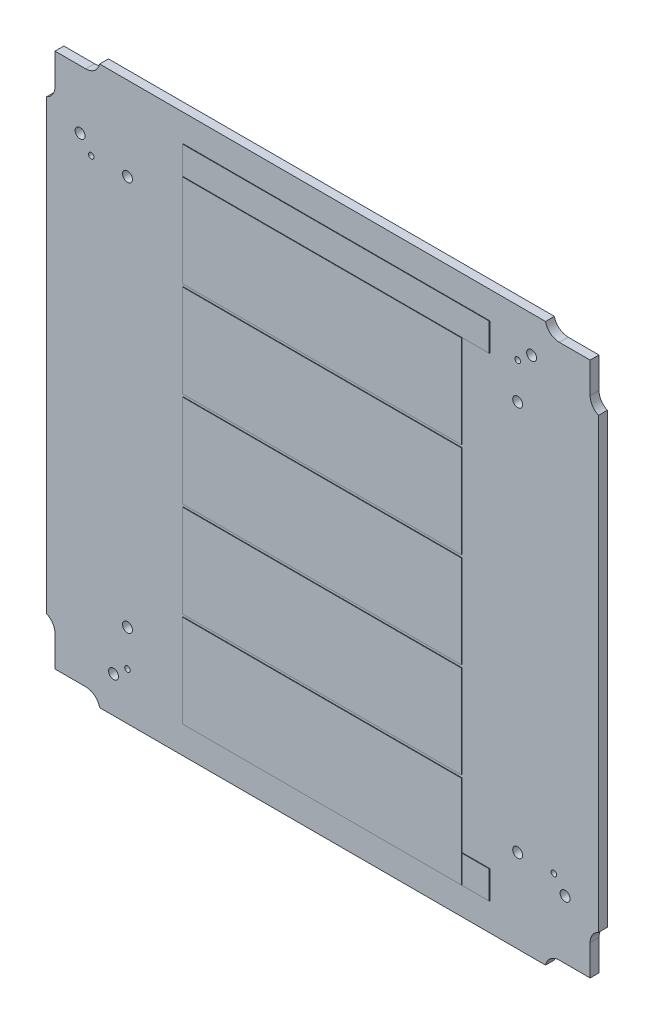
SolidWorks part; units mm, degrees
ref_plane "Front Plane" through (0, 0, 0) normal (0, 0, 1) x (1, 0, 0)
ref_plane "Top Plane" through (0, 0, 0) normal (0, 1, 0) x (1, 0, 0)
ref_plane "Right Plane" through (0, 0, 0) normal (1, 0, 0) x (0, 0, -1)
sketch "Sketch1" plane through (0, 0, 0) normal (0, 0, 1) x (1, 0, 0)
  line L0 (-40, 50) -> (-40, 48)
  line L1 (-50, -50) -> (50, -50)
  line L2 (-50, -50) -> (-50, 50)
  line L3 (-50, 50) -> (50, 50)
  line L4 (50, -50) -> (50, 50)
  line L5 (-50, -50) -> (50, 50) construction
  line L6 (-50, 50) -> (50, -50) construction
  line L7 (-50, 50) -> (-40, 50)
  line L8 (-50, 50) -> (-50, 40)
  line L9 (-40, 48) -> (-48, 48)
  line L10 (-48, 48) -> (-48, 40)
  line L11 (50, 50) -> (40, 50)
  line L12 (50, 50) -> (50, 40)
  line L13 (-48, 40) -> (-50, 40)
  line L14 (50, 40) -> (48, 40)
  line L15 (-50, -50) -> (-37.8649, -50)
  line L16 (-50, -50) -> (-50, -37.8649)
  line L17 (50, 50) -> (50, 40)
  line L18 (50, 50) -> (40, 50)
  line L19 (50, -50) -> (41.5, -50)
  line L20 (50, -50) -> (50, -41.5)
  line L21 (48, 40) -> (48, 48)
  line L22 (48, 48) -> (40, 48)
  line L23 (40, 48) -> (40, 50)
  line L24 (40, -50) -> (40, -48)
  line L25 (50, -50) -> (40, -50)
  line L26 (50, -50) -> (50, -40)
  line L27 (40, -48) -> (48, -48)
  line L28 (48, -48) -> (48, -40)
  line L29 (48, -40) -> (50, -40)
  line L30 (-50, -40) -> (-48, -40)
  line L31 (-50, -50) -> (-50, -40)
  line L32 (-50, -50) -> (-40, -50)
  line L33 (-48, -40) -> (-48, -48)
  line L34 (-48, -48) -> (-40, -48)
  line L35 (-40, -48) -> (-40, -50)
  point P0 (0, 0)
  point P38 (0, 0)
  dimension "D1" = 100
  dimension "D2" = 100
  dimension "D3" = 2
  dimension "D4" = 10
  dimension "D5" = 4
extrude "Boss-Extrude1" add sketch "Sketch1" along normal blind 1.5875 contours L1 L4 L3 L2 region at (0, 0, 0)
fillet "Fillet1" radius 2.54 8 edges at (-48, -40, 0.7937) (-40, -48, 0.7937) (40, -48, 0.7937) (48, -40, 0.7937) (48, 40, 0.7937) (40, 48, 0.7937) (-40, 48, 0.7937) (-48, 40, 0.7937)
sketch "Sketch5" plane through (0, 0, 1.5875) normal (0, 0, 1) x (1, 0, 0)
  line L0 (0, 50) -> (0, -50) construction
  line L5 (-40, 50) -> (40, 50) construction
  line L6 (-40, -50) -> (40, -50) construction
  line L8 (-35.7478, 50) -> (8.2522, 50) construction
  line L9 (-35.7478, 50) -> (-35.7478, 45.8) construction
  line L10 (-35.7478, 45.8) -> (8.2522, 45.8) construction
  line L11 (8.2522, 50) -> (8.2522, 45.8) construction
  circle A0 centre (-35, 43.55) radius 0.395
  circle A1 centre (-33, 43.55) radius 0.395
  circle A2 centre (-31, 43.55) radius 0.395
  circle A3 centre (-29, 43.55) radius 0.395
  circle A4 centre (-27, 43.55) radius 0.395
  circle A5 centre (-25, 43.55) radius 0.395
  circle A6 centre (-23, 43.55) radius 0.395
  circle A7 centre (-21, 43.55) radius 0.395
  circle A8 centre (-19, 43.55) radius 0.395
  circle A9 centre (-17, 43.55) radius 0.395
  circle A10 centre (-15, 43.55) radius 0.395
  circle A11 centre (-13, 43.55) radius 0.395
  circle A12 centre (-11, 43.55) radius 0.395
  circle A13 centre (-9, 43.55) radius 0.395
  circle A14 centre (-7, 43.55) radius 0.395
  circle A15 centre (-5, 43.55) radius 0.395
  circle A16 centre (-3, 43.55) radius 0.395
  circle A17 centre (-1, 43.55) radius 0.395
  circle A18 centre (1, 43.55) radius 0.395
  circle A19 centre (3, 43.55) radius 0.395
  circle A20 centre (5, 43.55) radius 0.395
  circle A21 centre (7, 43.55) radius 0.395
  circle A22 centre (-33, 41.55) radius 0.395
  circle A23 centre (-31, 41.55) radius 0.395
  circle A24 centre (-29, 41.55) radius 0.395
  circle A25 centre (-27, 41.55) radius 0.395
  circle A26 centre (-25, 41.55) radius 0.395
  circle A27 centre (-23, 41.55) radius 0.395
  circle A28 centre (-21, 41.55) radius 0.395
  circle A29 centre (-19, 41.55) radius 0.395
  circle A30 centre (-17, 41.55) radius 0.395
  circle A31 centre (-15, 41.55) radius 0.395
  circle A32 centre (-13, 41.55) radius 0.395
  circle A33 centre (-11, 41.55) radius 0.395
  circle A34 centre (-9, 41.55) radius 0.395
  circle A35 centre (-7, 41.55) radius 0.395
  circle A36 centre (-5, 41.55) radius 0.395
  circle A37 centre (-3, 41.55) radius 0.395
  circle A38 centre (-1, 41.55) radius 0.395
  circle A39 centre (1, 41.55) radius 0.395
  circle A40 centre (3, 41.55) radius 0.395
  circle A41 centre (5, 41.55) radius 0.395
  circle A42 centre (7, 41.55) radius 0.395
  circle A43 centre (-35, 41.55) radius 0.395
  dimension "D5" = 0.79
  dimension "D2" = 2.25
  dimension "D3" = 2
  dimension "D4" = 2
  dimension "D8" = 29
  dimension "D9" = 44
  dimension "D10" = 4.2
  dimension "D6" = 22
  dimension "D7" = 2
sketch "Sketch6" plane through (0, 0, 1.5875) normal (0, 0, 1) x (1, 0, 0)
  line L0 (-40, 50) -> (40, 50) construction
  line L1 (-49.5, 50) -> (49.5, 50)
  line L2 (-49.5, 50) -> (-49.5, -50)
  line L3 (-49.5, -50) -> (49.5, -50)
  line L4 (49.5, 50) -> (49.5, -50)
  line L5 (-40, -50) -> (40, -50) construction
  line L6 (50, -40) -> (50, 40) construction
  dimension "D1" = 99
  dimension "D2" = 0.5
extrude "Cut-Extrude2" cut sketch "Sketch6" against normal through all flip side to cut
sketch "Sketch2" plane through (0, 0, 1.5875) normal (0, 0, 1) x (1, 0, 0)
  line L0 (-36.5, 41) -> (36.5, 41)
  line L1 (-39, 38.5) -> (-36.5, 41)
  line L2 (39, 38.5) -> (39, 26.5)
  line L3 (36.5, 24) -> (-36.5, 24)
  line L4 (-39, 26.5) -> (-39, 38.5)
  line L5 (-36.5, 24) -> (-39, 26.5)
  line L6 (0, 0) -> (0, 50) construction
  line L7 (36.5, 41) -> (39, 38.5)
  line L8 (39, 26.5) -> (36.5, 24)
  line L9 (-36.5, 22.75) -> (36.5, 22.75)
  line L10 (-39, 20.25) -> (-36.5, 22.75)
  line L11 (39, 20.25) -> (39, 8.25)
  line L12 (36.5, 5.75) -> (-36.5, 5.75)
  line L13 (-39, 8.25) -> (-39, 20.25)
  line L14 (-36.5, 5.75) -> (-39, 8.25)
  line L15 (36.5, 22.75) -> (39, 20.25)
  line L16 (39, 8.25) -> (36.5, 5.75)
  line L17 (-36.5, 4.5) -> (36.5, 4.5)
  line L18 (-39, 2) -> (-36.5, 4.5)
  line L19 (39, 2) -> (39, -10)
  line L20 (36.5, -12.5) -> (-36.5, -12.5)
  line L21 (-39, -10) -> (-39, 2)
  line L22 (-36.5, -12.5) -> (-39, -10)
  line L23 (36.5, 4.5) -> (39, 2)
  line L24 (39, -10) -> (36.5, -12.5)
  line L25 (-36.5, -13.75) -> (36.5, -13.75)
  line L26 (-39, -16.25) -> (-36.5, -13.75)
  line L27 (39, -16.25) -> (39, -28.25)
  line L28 (36.5, -30.75) -> (-36.5, -30.75)
  line L29 (-39, -28.25) -> (-39, -16.25)
  line L30 (-40, 50) -> (40, 50) construction
  line L33 (-36.5, -30.75) -> (-39, -28.25)
  line L34 (36.5, -13.75) -> (39, -16.25)
  line L36 (39, -28.25) -> (36.5, -30.75)
  line L37 (-36.5, -32) -> (36.5, -32)
  line L38 (-39, -34.5) -> (-36.5, -32)
  line L39 (39, -34.5) -> (39, -46.5)
  line L40 (36.5, -49) -> (-36.5, -49)
  line L41 (-39, -46.5) -> (-39, -34.5)
  line L42 (-36.5, -49) -> (-39, -46.5)
  line L43 (36.5, -32) -> (39, -34.5)
  line L44 (39, -46.5) -> (36.5, -49)
  line L45 (-40, -50) -> (40, -50) construction
  point P0 (-39, 41)
  point P3 (39, 41)
  point P4 (39, 24)
  point P5 (-39, 24)
  point P19 (-39, 22.75)
  point P21 (39, 22.75)
  point P22 (39, 5.75)
  point P23 (-39, 5.75)
  point P31 (-39, 4.5)
  point P33 (39, 4.5)
  point P34 (39, -12.5)
  point P35 (-39, -12.5)
  point P43 (-39, -13.75)
  point P45 (39, -13.75)
  point P46 (39, -30.75)
  point P47 (-39, -30.75)
  point P55 (-39, -32)
  point P57 (39, -32)
  point P58 (39, -49)
  point P59 (-39, -49)
  dimension "D1" = 78
  dimension "D2" = 17
  dimension "D3" = 5
  dimension "D4" = 1
  dimension "D5" = 9
hole_wizard "Ø1.0 (1) Diameter Hole1" positions "Sketch8" profile "Sketch9" hole size "Ø1.0" standard "ISO" end condition through all
sketch "Sketch8" plane through (0, 0, 1.5875) normal (0, 0, 1) x (1, 0, 0)
  line L0 (-49.5, 40.1646) -> (-49.5, -40.1646) construction
  line L2 (-40, 50) -> (40, 50) construction
  point P0 (-41.5, 35)
  dimension "D1" = 8
  dimension "D2" = 15
sketch "Sketch9" plane through (-41.5, 35, 1.5875) normal (1, 0, 0) x (0, -1, 0)
  line L0 (0, 0) -> (0, 1.5875)
  line L1 (0, 1.5875) -> (0.5, 1.5875)
  line L2 (0.5, 1.5875) -> (0.5, 0)
  line L5 (0.5, 0) -> (0, 0)
  line L11 (0, -6.35) -> (0, 107.95) construction
  dimension "Thru Hole Dia." = 1
  dimension "Thru Hole Depth" = 1.5875
hole_wizard "#0 Clearance Hole1" positions "Sketch11" profile "Sketch10" hole size "#0" standard "ANSI Inch" end condition through all
sketch "Sketch11" plane through (0, 0, 1.5875) normal (0, 0, 1) x (1, 0, 0)
  point P0 (-43.5, 37.5)
  point P4 (-35, 35)
sketch "Sketch10" plane through (-43.5, 37.5, 1.5875) normal (1, 0, 0) x (0, -1, 0)
  line L0 (0, 0) -> (0, 1.5875)
  line L1 (0, 1.5875) -> (0.889, 1.5875)
  line L2 (0.889, 1.5875) -> (0.889, 0)
  line L5 (0.889, 0) -> (0, 0)
  line L11 (0, -6.35) -> (0, 107.95) construction
  dimension "Thru Hole Dia." = 1.778
  dimension "Thru Hole Depth" = 1.5875
ref_axis "Axis1" through (0, 0, 0) along (0, 0, 1)
pattern_circular "CirPattern1" count 4 over 360 about axis through (0, 0, 0) along (0, 0, 1) of "Ø1.0 (1) Diameter Hole1", "#0 Clearance Hole1"
sketch "Sketch12" plane through (0, 0, 1.5875) normal (0, 0, 1) x (1, 0, 0)
  line L0 (-25, 22.9) -> (25, 22.9)
  line L1 (-25, 40) -> (25, 40)
  line L2 (-25, 40) -> (-25, 23.4)
  line L3 (-25, 23.4) -> (25, 23.4)
  line L4 (25, 40) -> (25, 23.4)
  line L5 (-25, 22.9) -> (-25, 6.3)
  line L6 (-25, 6.3) -> (25, 6.3)
  line L7 (25, 22.9) -> (25, 6.3)
  line L8 (-25, 5.8) -> (25, 5.8)
  line L9 (-25, 5.8) -> (-25, -10.8)
  line L10 (-25, -10.8) -> (25, -10.8)
  line L11 (25, 5.8) -> (25, -10.8)
  line L12 (-25, -11.3) -> (25, -11.3)
  line L13 (-25, -11.3) -> (-25, -27.9)
  line L14 (-25, -27.9) -> (25, -27.9)
  line L15 (25, -11.3) -> (25, -27.9)
  line L16 (-25, -28.4) -> (25, -28.4)
  line L17 (-25, -28.4) -> (-25, -45)
  line L18 (-25, -45) -> (25, -45)
  line L19 (25, -28.4) -> (25, -45)
  line L20 (-40, -50) -> (40, -50) construction
  line L21 (0, 0) -> (0, -10.8) construction
  dimension "D1" = 0.5
  dimension "D2" = 50
  dimension "D4" = 85
  dimension "D5" = 5
  dimension "D3" = 5
extrude "Boss-Extrude2" add sketch "Sketch12" along normal blind 0.1
sketch "Sketch13" plane through (0, 0, 1.5875) normal (0, 0, 1) x (1, 0, 0)
  line L0 (-25, -45) -> (25, -45) construction
  line L1 (-25, 40.1) -> (30, 40.1)
  line L2 (-25, 40.1) -> (-25, 45.1)
  line L3 (-25, 45.1) -> (30, 45.1)
  line L4 (30, 40.1) -> (30, 45.1)
  line L5 (25.1, -45) -> (30, -45)
  line L6 (25.1, -45) -> (25.1, -40)
  line L7 (25.1, -40) -> (30, -40)
  line L8 (30, -45) -> (30, -40)
  line L9 (25, -45) -> (25, -28.4) construction
  line L10 (-25, 40) -> (-25, 23.4) construction
  line L11 (25, 40) -> (-25, 40) construction
  dimension "D1" = 0.1
  dimension "D2" = 5
  dimension "D3" = 55
  dimension "D4" = 0.1
extrude "Boss-Extrude3" add sketch "Sketch13" along normal blind 0.1
